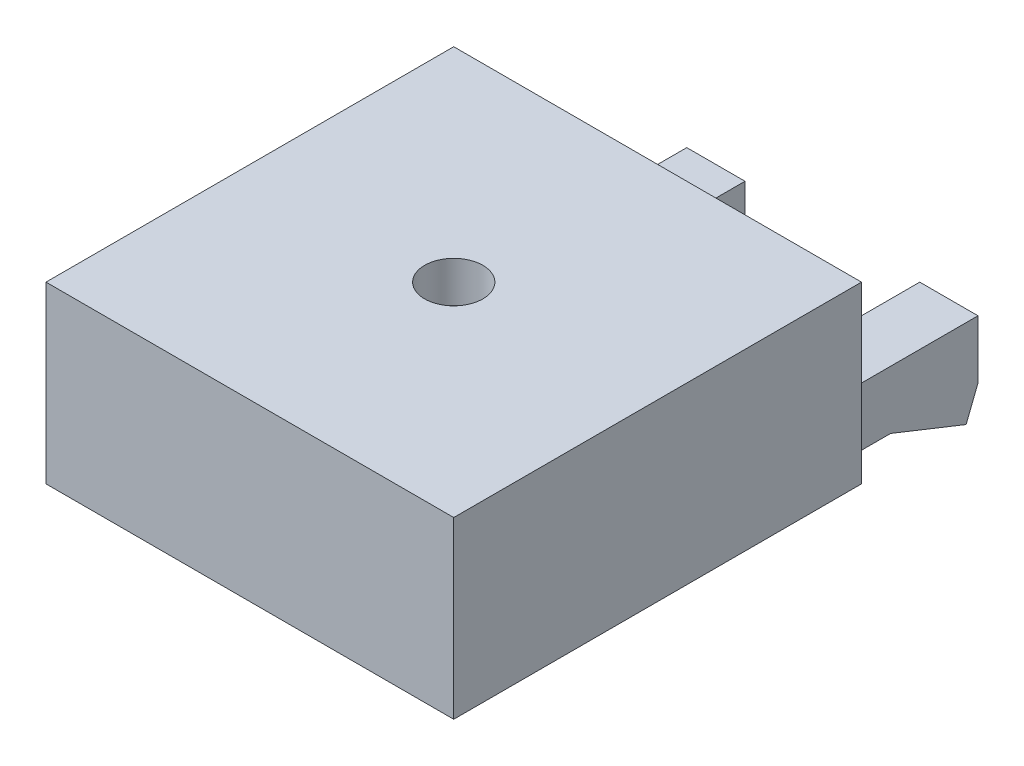
SolidWorks part; units mm, degrees
ref_plane "Plan de face" through (0, 0, 0) normal (0, 0, 1) x (1, 0, 0)
ref_plane "Plan de dessus" through (0, 0, 0) normal (0, 1, 0) x (1, 0, 0)
ref_plane "Plan de droite" through (0, 0, 0) normal (1, 0, 0) x (0, 0, -1)
sketch "Esquisse1" plane through (0, 0, 0) normal (0, 1, 0) x (1, 0, 0)
  line L1 (0, 0) -> (70, 0)
  line L2 (0, 0) -> (0, 70)
  line L3 (0, 70) -> (70, 70)
  line L4 (70, 0) -> (70, 70)
  dimension "D1" = 70
  dimension "D2" = 70
extrude "Boss.-Extru.4" add sketch "Esquisse1" along normal blind 30
sketch "Esquisse5" plane through (0, 0, 0) normal (0, -1, 0) x (-1, 0, 0)
  line L0 (-70, 0) -> (-70, 70) construction
  line L1 (-5, 5) -> (-65, 5)
  line L2 (-5, 5) -> (-5, 65)
  line L3 (-5, 65) -> (-65, 65)
  line L4 (-65, 5) -> (-65, 65)
  line L5 (0, 70) -> (0, 0) construction
  line L6 (0, 0) -> (-70, 0) construction
  line L7 (-70, 70) -> (0, 70) construction
  dimension "D1" = 5
  dimension "D2" = 5
  dimension "D3" = 5
  dimension "D4" = 5
extrude "Enlèv. mat.-Extru.3" cut sketch "Esquisse5" against normal blind 23
sketch "Esquisse6" plane through (0, 23, 0) normal (0, -1, 0) x (-1, 0, 0)
  line L0 (0, 0) -> (-70, 0) construction
  line L1 (0, 70) -> (0, 0) construction
  circle A0 centre (-35, 35) radius 5
  dimension "D1" = 10
  dimension "D2" = 35
  dimension "D3" = 35
extrude "Enlèv. mat.-Extru.4" cut sketch "Esquisse6" against normal blind 23 contours A0
sketch "Esquisse24" plane through (0, 0, -70) normal (0, 0, -1) x (-1, 0, 0)
  line L0 (0, 30) -> (-10.005, 30)
  line L1 (-70, 30) -> (0, 30) construction
  line L2 (-20.005, 30) -> (-50.005, 30)
  line L3 (-50.005, 30) -> (-60.005, 30)
  line L4 (-60.005, 30) -> (-60.005, 0)
  line L5 (-70, 0) -> (0, 0) construction
  line L10 (-60.005, 0) -> (-50.005, 0)
  line L11 (-50.005, 0) -> (-20.005, 0)
  line L12 (-20.005, 0) -> (-10.005, 0)
  dimension "D1" = 10
  dimension "D2" = 10.005
  dimension "D3" = 10
  dimension "D4" = 30
sketch "Esquisse28" plane through (0, 0, 0) normal (0, -1, 0) x (1, 0, 0)
  line L0 (50.005, -70) -> (60.005, -70) construction
  line L1 (50.005, -70) -> (60.005, -70)
  line L2 (50.005, -70) -> (50.005, -100)
  line L3 (50.005, -100) -> (60.005, -100)
  line L4 (60.005, -70) -> (60.005, -100)
  dimension "D1" = 30
extrude "Boss.-Extru.8" add sketch "Esquisse28" along normal mid plane 10
sketch "Esquisse29" plane through (60.005, 0, 0) normal (1, 0, 0) x (0, 0, -1)
  line L0 (70, -5) -> (85, -5)
  line L1 (100, -5) -> (97.2832, -11.8754)
  line L2 (100, -5) -> (70, -5) construction
  line L3 (97.2832, -11.8754) -> (98.6416, -8.4377)
  line L4 (98.6416, -8.4377) -> (97.9624, -10.1566)
  line L5 (97.9624, -10.1566) -> (85, -5)
  line M5 (70, -5) -> (100, -5)
extrude "Boss.-Extru.9" add sketch "Esquisse29" against normal blind 10 contours L5 L1 M5 region at (60.005, -6.7189, -94.3208)
sketch "Esquisse30" plane through (0, 0, 0) normal (0, -1, 0) x (1, 0, 0)
  line L0 (0, -70) -> (10.005, -70) construction
  line L1 (10.005, -70) -> (20.005, -70)
  line L2 (10.005, -70) -> (10.005, -100)
  line L3 (10.005, -100) -> (20.005, -100)
  line L4 (20.005, -70) -> (20.005, -100)
  dimension "D1" = 30
extrude "Boss.-Extru.10" add sketch "Esquisse30" along normal mid plane 10
sketch "Esquisse39" plane through (10.005, 0, 0) normal (-1, 0, 0) x (0, 0, 1)
  line L0 (-100, -5) -> (-95.9609, -15.2316)
  line L1 (-95.9609, -15.2316) -> (-85, -5)
  line L2 (-70, -5) -> (-100, -5) construction
  line L3 (-85, -5) -> (-100, -5)
  dimension "D1" = 11
extrude "Boss.-Extru.14" add sketch "Esquisse39" against normal blind 10
sketch "Esquisse40" plane through (0, -34.8279, -88.2251) normal (0, -0.3672, -0.9301) x (-1, 0, 0)
  line L0 (-20.005, 21.0679) -> (-20.005, 22.0679)
  line L1 (-20.005, 32.0679) -> (-20.005, 21.0679) construction
  line L2 (-20.005, 22.0679) -> (-10.005, 21.0679)
  line L3 (-10.005, 21.0679) -> (-20.005, 21.0679)
  dimension "D1" = 1
extrude "Enlèv. mat.-Extru.6" cut sketch "Esquisse40" against normal blind 10
